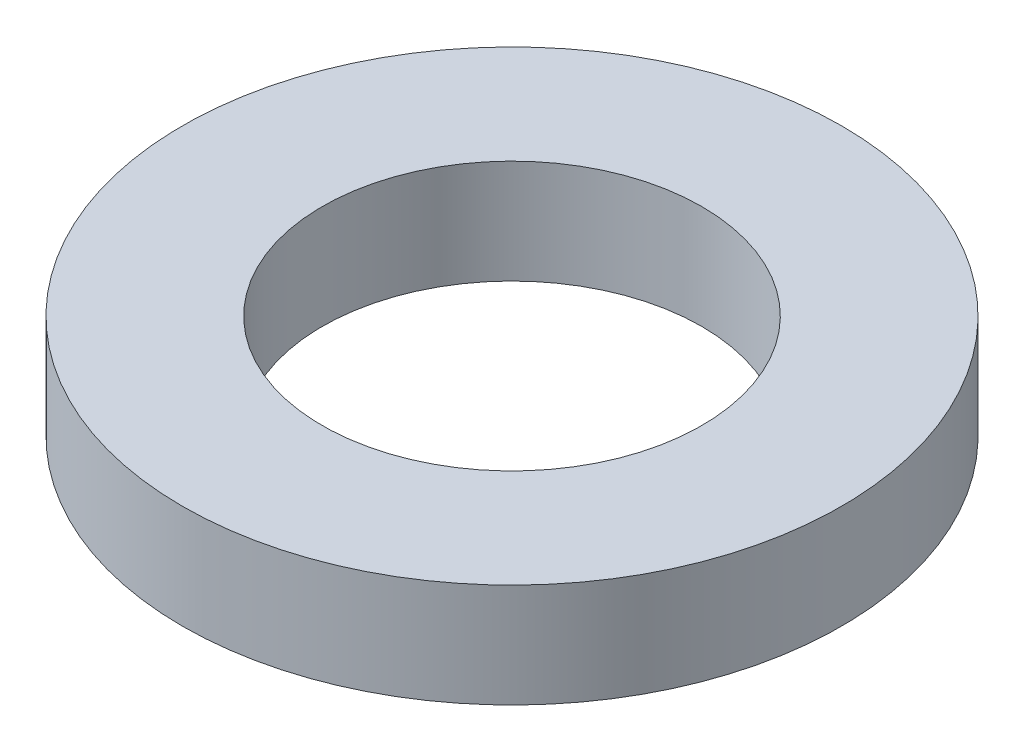
SolidWorks part; units mm, degrees
ref_plane "Front Plane" through (0, 0, 0) normal (0, 0, 1) x (1, 0, 0)
ref_plane "Top Plane" through (0, 0, 0) normal (0, 1, 0) x (1, 0, 0)
ref_plane "Right Plane" through (0, 0, 0) normal (1, 0, 0) x (0, 0, -1)
sketch "Sketch1" plane through (0, 0, 0) normal (0, 1, 0) x (1, 0, 0)
  circle A0 centre (0, 0) radius 82.5
  dimension "FLANGE_OD" = 165
extrude "Boss-Extrude1" add sketch "Sketch1" along normal blind 26
sketch "Sketch2" plane through (0, 0, 0) normal (0, 1, 0) x (1, 0, 0)
  circle A0 centre (0, 0) radius 47.5
  dimension "BORE_D" = 95
extrude "Cut-Extrude1" cut sketch "Sketch2" along normal through all
sketch "Sketch3" plane through (0, 26, 0) normal (0, 1, 0) x (1, 0, 0)
  circle A0 centre (0, 0) radius 33.7447 construction
  circle A1 centre (-33.7447, 0) radius 3.4879
  dimension "BOLT_D" = 6.9759
  dimension "BOLT_PCD" = 67.4894
extrude "Cut-Extrude2" cut sketch "Sketch3" against normal blind 21.7871 rebuild error yes
pattern_circular "CirPattern1" count 3 over 360 rebuild error yes
